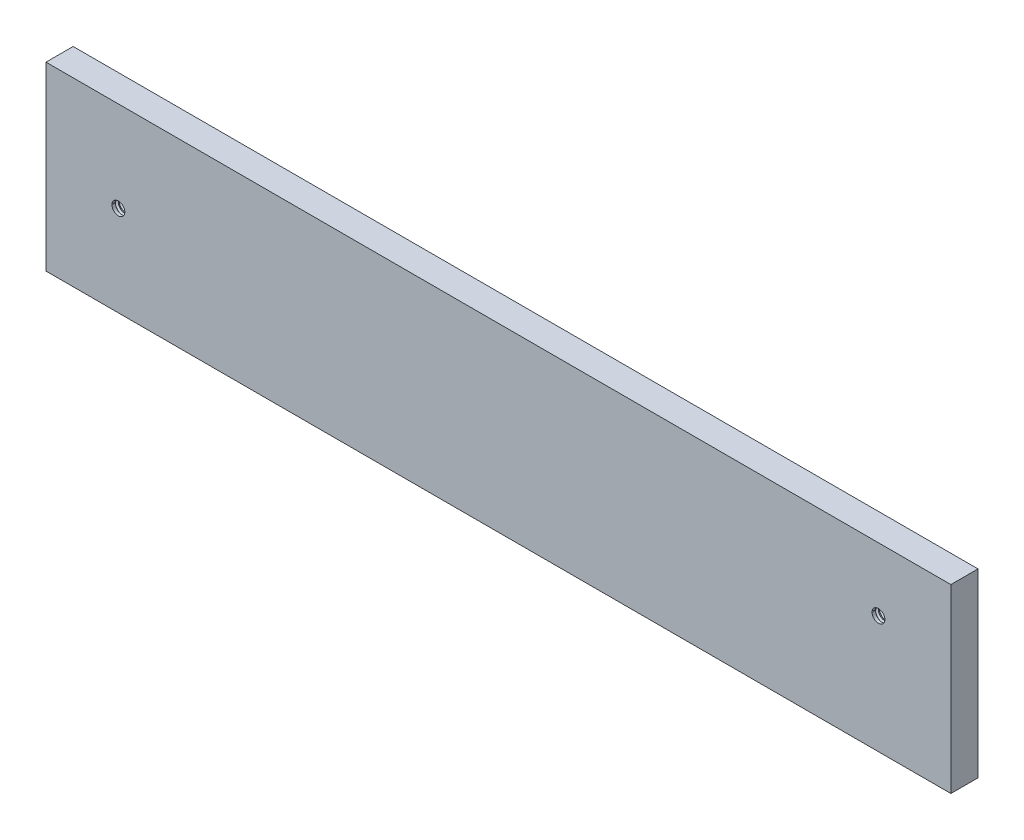
SolidWorks part; units mm, degrees
ref_plane "Front Plane" through (0, 0, 0) normal (0, 0, 1) x (1, 0, 0)
ref_plane "Top Plane" through (0, 0, 0) normal (0, 1, 0) x (1, 0, 0)
ref_plane "Right Plane" through (0, 0, 0) normal (1, 0, 0) x (0, 0, -1)
sketch "Sketch1" plane through (0, 0, 0) normal (0, 0, 1) x (1, 0, 0)
  line L1 (-34.5587, 7.5712) -> (124.1913, 7.5712)
  line L2 (-34.5587, 7.5712) -> (-34.5587, -24.1788)
  line L3 (-34.5587, -24.1788) -> (124.1913, -24.1788)
  line L4 (124.1913, 7.5712) -> (124.1913, -24.1788)
  dimension "D1" = 31.75
  dimension "D2" = 158.75
extrude "Boss-Extrude1" add sketch "Sketch1" against normal blind 4.7625
sketch "Sketch2" plane through (0, 0, 0) normal (0, 0, 1) x (1, 0, 0)
  line L0 (-34.5587, 7.5712) -> (-34.5587, -24.1788) construction
  line L1 (124.1913, 7.5712) -> (-34.5587, 7.5712) construction
  line L2 (124.1913, -24.1788) -> (124.1913, 7.5712) construction
  circle A0 centre (-21.8587, -8.3038) radius 1.1303
  circle A1 centre (111.4913, -3.5413) radius 1.1303
  dimension "D1" = 2.2606
  dimension "D3" = 2.2606
  dimension "D2" = 12.7
  dimension "D4" = 11.1125
  dimension "D5" = 12.7
  dimension "D6" = 15.875
extrude "Cut-Extrude1" cut sketch "Sketch2" against normal through all
thread "Thread1" pitch 0.635 method cut profile "Thread Profile1" start angle 0, offset 0, length 10, pitch 0.635, diameter 2.2606
ref_plane "Plane1" through (110.361, -3.5413, 0) normal (0, -1, 0) x (-1, 0, 0)
sketch "Thread Profile1" plane through (110.361, -3.5413, 0) normal (0, -1, 0) x (-1, 0, 0)
  line L0 (0, 0) -> (0, 0.635) construction
  line L1 (0, 0) -> (0.3437, 0.1984)
  line L2 (0.3437, 0.1984) -> (0.3437, 0.2778)
  line L3 (0.3437, 0.2778) -> (0, 0.4762)
  line L4 (0.3437, 0.2381) -> (0, 0.2381) construction
  line L11 (0, 0) -> (0, 0.4762)
  point P2 (0, 0)
  dimension "Pitch" = 0.635
  dimension "Profile_Angle" = 60
  dimension "Profile_Land" = 0.0794
  dimension "Profile_Height" = 0.3437
thread "Thread2" pitch 0.635 method cut profile "Thread Profile2" start angle 0, offset 0, length 10, pitch 0.635, diameter 2.2606
ref_plane "Plane2" through (-22.989, -8.3038, 0) normal (0, -1, 0) x (-1, 0, 0)
sketch "Thread Profile2" plane through (-22.989, -8.3038, 0) normal (0, -1, 0) x (-1, 0, 0)
  line L0 (0, 0) -> (0, 0.635) construction
  line L1 (0, 0) -> (0.3437, 0.1984)
  line L2 (0.3437, 0.1984) -> (0.3437, 0.2778)
  line L3 (0.3437, 0.2778) -> (0, 0.4762)
  line L4 (0.3437, 0.2381) -> (0, 0.2381) construction
  line L11 (0, 0) -> (0, 0.4762)
  point P2 (0, 0)
  dimension "Pitch" = 0.635
  dimension "Profile_Angle" = 60
  dimension "Profile_Land" = 0.0794
  dimension "Profile_Height" = 0.3437
